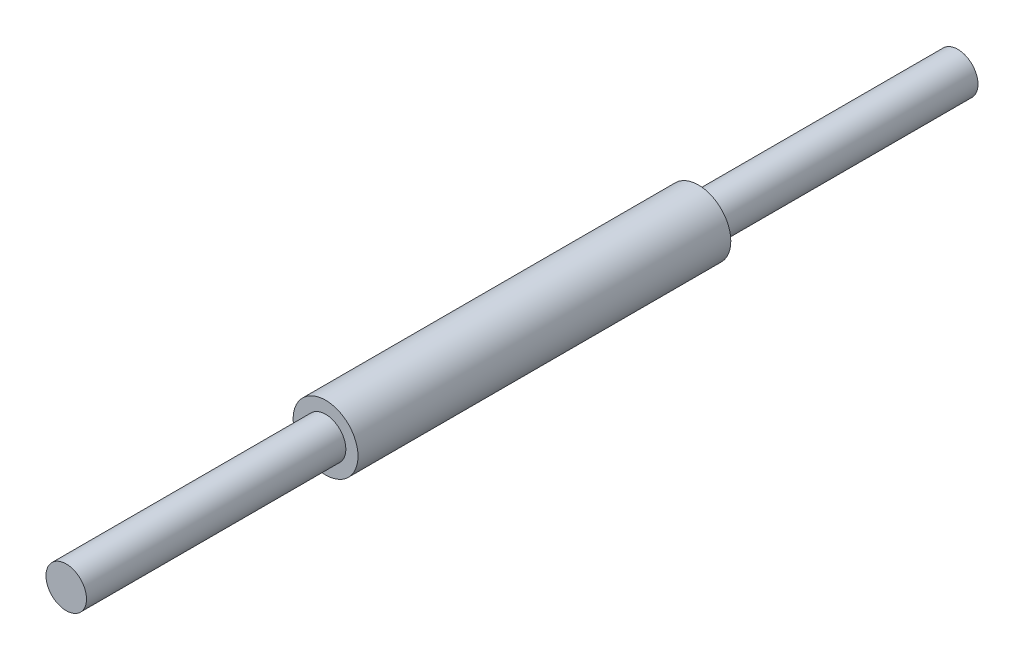
SolidWorks part; units mm, degrees
ref_plane "Front Plane" through (0, 0, 0) normal (0, 0, 1) x (1, 0, 0)
ref_plane "Top Plane" through (0, 0, 0) normal (0, 1, 0) x (1, 0, 0)
ref_plane "Right Plane" through (0, 0, 0) normal (1, 0, 0) x (0, 0, -1)
sketch "Sketch2" plane through (0, 0, 0) normal (0, 0, 1) x (1, 0, 0)
  circle A0 centre (0, 0) radius 3.175
  dimension "D1" = 6.35
extrude "Boss-Extrude1" add sketch "Sketch2" along normal blind 69.85 and the other way blind 69.85
sketch "Sketch3" plane through (0, 0, 0) normal (0, 0, 1) x (1, 0, 0)
  circle A0 centre (0, 0) radius 5.08
  dimension "D1" = 10.16
extrude "Boss-Extrude2" add sketch "Sketch3" along normal blind 29.21 and the other way blind 29.21
